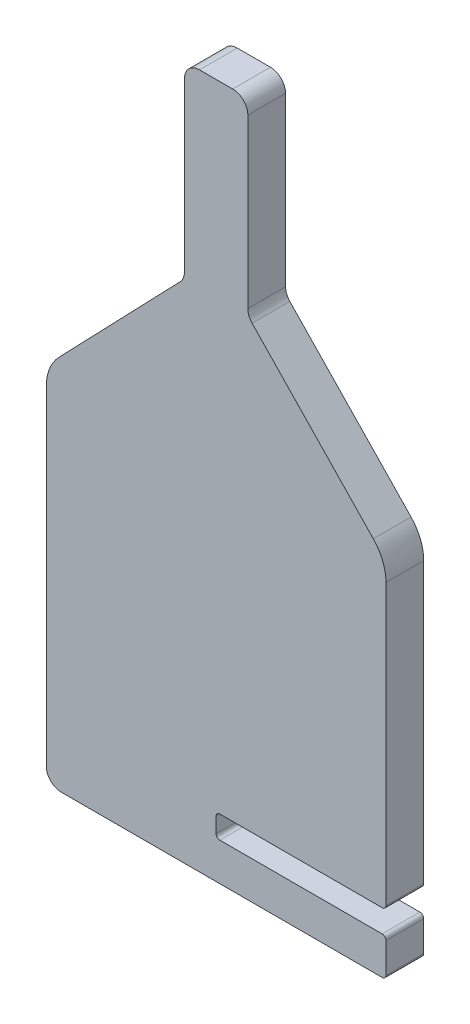
SolidWorks part; units mm, degrees
ref_plane "Alzado" through (0, 0, 0) normal (0, 0, 1) x (1, 0, 0)
ref_plane "Planta" through (0, 0, 0) normal (0, 1, 0) x (1, 0, 0)
ref_plane "Vista lateral" through (0, 0, 0) normal (1, 0, 0) x (0, 0, -1)
sketch "Croquis1" plane through (0, 0, 0) normal (0, 0, 1) x (1, 0, 0)
  line L0 (-4.2, 20) -> (-22.5, 0.9719)
  line L1 (-4.2, 45) -> (4.2, 45)
  line L2 (-22.5, 0.9719) -> (-22.5, -47.0281)
  line L3 (-22.5, -47.0281) -> (22.5, -47.0281)
  line L4 (22.5, 0.9719) -> (22.5, -47.0281)
  line L5 (-4.2, 45) -> (4.2, 45)
  line L6 (-4.2, 45) -> (-4.2, 20)
  line L8 (4.2, 45) -> (4.2, 19.999)
  line L9 (4.2, 19.999) -> (22.5, 0.9719)
  line L10 (0, 72.8664) -> (0, -82.626) construction
  dimension "D1" = 45
  dimension "D2" = 25
  dimension "D3" = 4.2
  dimension "D4" = 22.5
  dimension "D5" = 45
  dimension "D6" = 4.2
  dimension "D7" = 26.3993
  dimension "D8" = 26.4
  dimension "D9" = 48
  dimension "D10" = 48
extrude "Saliente-Extruir1" add sketch "Croquis1" along normal blind 5 contours L6 L0 L2 L3 L4 L9 L8 L1
sketch "Croquis3" plane through (0, 0, 5) normal (0, 0, 1) x (1, 0, 0)
  line L0 (22.5, 0.9719) -> (22.5, -47.0281) construction
  line L1 (22.5, -39.0281) -> (0, -39.0281)
  line L2 (22.5, -39.0281) -> (22.5, -42.0281)
  line L3 (22.5, -42.0281) -> (0, -42.0281)
  line L4 (0, -39.0281) -> (0, -42.0281)
  line L5 (-22.5, -47.0281) -> (22.5, -47.0281) construction
  dimension "D1" = 3
  dimension "D2" = 5
  dimension "D3" = 22.5
extrude "Cortar-Extruir2" cut sketch "Croquis3" against normal up to surface (5 mm away) up to face at (0, 4.7358, 0)
fillet "Redondeo1" radius 2 5 edges at (-22.5, -47.0281, 2.5) (-4.2, 20, 2.5) (-4.2, 45, 2.5) (4.2, 19.999, 2.5) (4.2, 45, 2.5)
fillet "Redondeo2" radius 6 2 edges at (-22.5, 0.9719, 2.5) (22.5, 0.9719, 2.5)
fillet "Redondeo3" radius 0.5 5 edges at (22.5, -47.0281, 2.5) (0, -42.0281, 2.5) (0, -39.0281, 2.5) (22.5, -39.0281, 2.5) (22.5, -42.0281, 2.5)
